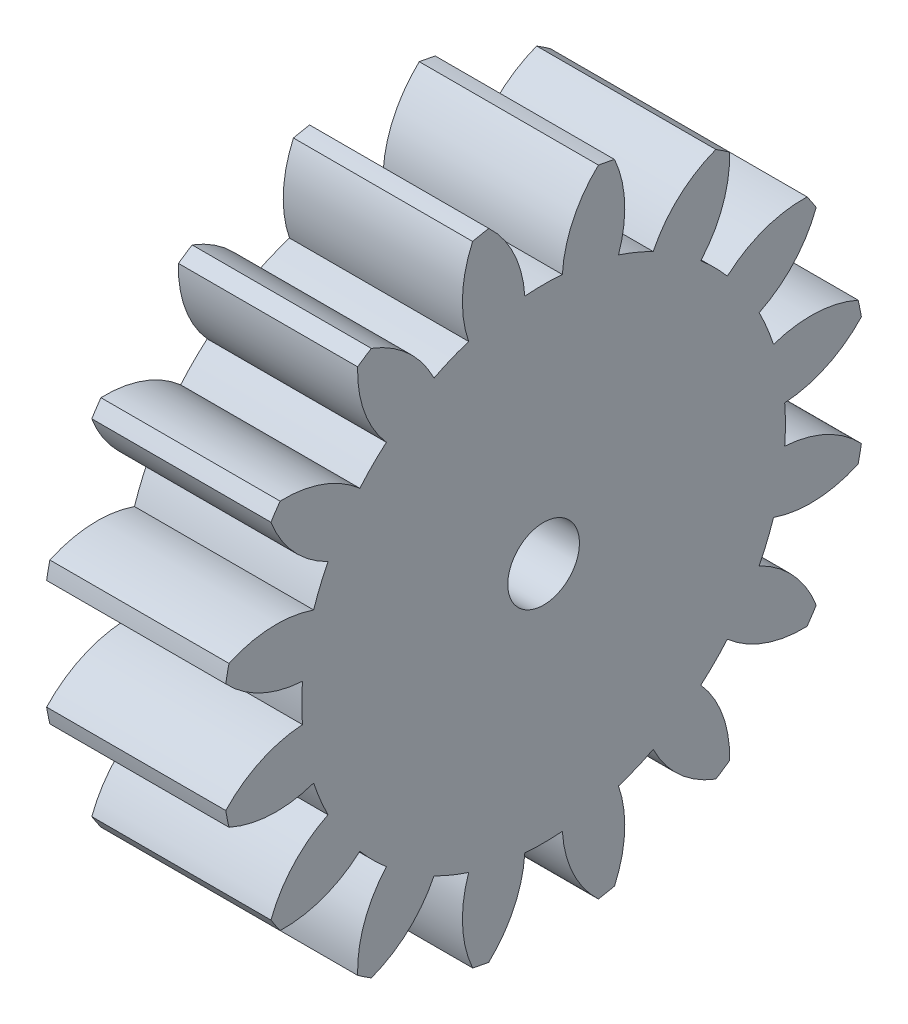
SolidWorks part; units mm, degrees
material "1.0035 (S185)"
ref_plane "Plane1" through (0, 0, 0) normal (0, 0, 1) x (1, 0, 0)
ref_plane "Plane2" through (0, 0, 0) normal (0, 1, 0) x (1, 0, 0)
ref_plane "Plane3" through (0, 0, 0) normal (1, 0, 0) x (0, 0, -1)
sketch "HoldingSke" plane through (0, 0, 0) normal (0, 1, 0) x (1, 0, 0)
  line L0 (0, 0) -> (0.9613, -0.2756)
  line L1 (-15, 0) -> (100, 0) construction
  line L2 (0, 0) -> (-2.1039, 2.3779)
  line L3 (0, 0) -> (-11.863, 4.5341)
  line L4 (0, 0) -> (8.3015, 2.3804)
  line L5 (0, 0) -> (-46.8476, -17.4728)
  line L6 (0, 0) -> (-4.1448, -2.7965)
  line L7 (-2.1039, 2.3779) -> (8.6586, 51.2059)
  line L8 (-76.2, 54.61) -> (-75.9, 54.61)
  line L9 (-71.009, 38.7566) -> (-53.1078, 45.2721)
  line L10 (-76.2, 71.12) -> (104.1128, 71.12)
  line L11 (0, 0) -> (-5, 0)
  line L12 (-76.2, 101.6) -> (-76.162, 101.6)
  line L13 (24.9733, 27.94) -> (52.9518, 28.4284)
  line L14 (24.9733, 27.94) -> (24.9743, 27.94)
  line L15 (24.9733, 27.94) -> (100.4006, 29.5858)
  line L16 (-63.627, -1) -> (-12.827, -1)
  circle A0 centre (0, 0) radius 1
  circle A1 centre (0, 0) radius 6.749
  circle A2 centre (0, 0) radius 37.5
  circle A3 centre (0, 0) radius 1
  dimension "MHD" = 13.498
  dimension "Hub_dia" = 75
  dimension "Bore" = 2
  dimension "MBD" = 2
  dimension "Num_teeth" = 16
  dimension "Pitch_radius" = 180.3128
  dimension "Pitch" = 1
  dimension "Width" = 5
  dimension "Overall_len" = 50
  dimension "Show_teeth" = 16
  dimension "Thickness" = 5
  dimension "OAL" = 50.0001
  dimension "T_dim" = 0.3
  dimension "Ap" = 20
  dimension "H" = 19.05
  dimension "Backlash" = 0.038
  dimension "Addendum_fac" = 1
  dimension "Dedendum_fac" = 1.25
  dimension "Clearance_fac" = 0.25
  dimension "Dedendum_add" = 0.001
  dimension "Module" = 1
sketch "BasProSke" plane through (0, 0, 0) normal (0, 1, 0) x (1, 0, 0)
  line L0 (-10, 0) -> (60, 0) construction
  line L1 (0, 0) -> (0, 9)
  line L2 (0, 0) -> (5, 0)
  line L3 (5, 0) -> (5, 9)
  line L4 (5, 9) -> (0, 9)
  dimension "Diameter" = 18
  dimension "Thickness" = 5
revolve "Base-Revolve" add sketch "BasProSke" angle 360 about L0
sketch "TooCutSke" plane through (0, 0, 0) normal (1, 0, 0) x (0, 0, -1)
  line L1 (0, 0) -> (0, 107) construction
  line L2 (0, 0) -> (-0.8506, 7.9547) construction
  line L3 (0, 0) -> (-3.1089, 15.6293) construction
  line L4 (-0.8506, 7.9547) -> (-1.5544, 7.8146) construction
  arc A0 (0.5238, 6.7286) -> (-0.5238, 6.7286) centre (0, 0) ccw
  arc A1 (1.5534, 8.8907) -> (-1.5534, 8.8907) centre (0, 0) ccw
  circle A2 centre (0, 0) radius 8 construction
  circle A3 centre (0, 0) radius 7.5175 construction
  arc A4 (-0.5238, 6.7286) -> (-1.5534, 8.8907) centre (-3.7179, 6.5338) ccw
  arc A5 (1.5534, 8.8907) -> (0.5238, 6.7286) centre (3.7179, 6.5338) ccw
  dimension "Root_dia" = 13.498
  dimension "Overcut_dia" = 18.0508
  dimension "Pitch_dia" = 16
  dimension "Base_dia" = 15.0351
  dimension "Flank_rad" = 3.2
  dimension "Half_ang" = 11.25
  dimension "Half_CT" = 0.7176
extrude "ToothCut" cut sketch "TooCutSke" along normal through all
fillet "Breaks" [suppressed] radius 0.02 tangent propagation no
fillet "RootFillets" [suppressed] radius 0.251
pattern_circular "TeethCuts" count 16 every 22.5 about axis through (-10, 0, 0) along (1, 0, 0) of "ToothCut", "RootFillets", "Breaks"
sketch "HubNeaOneSke" plane through (0, 0, 0) normal (-1, 0, 0) x (0, 0, 1)
  circle A0 centre (0, 0) radius 6.749
  dimension "Diameter" = 13.498
extrude "HubNearOne" [suppressed] add sketch "HubNeaOneSke" along normal blind 45.0001
sketch "HubNeaBotSke" plane through (0, 0, 0) normal (-1, 0, 0) x (0, 0, 1)
  circle A0 centre (0, 0) radius 6.749
  dimension "Diameter" = 13.498
extrude "HubNearBoth" [suppressed] add sketch "HubNeaBotSke" along normal blind 22.5
ref_plane "FarPln" through (5, 0, 0) normal (1, 0, 0) x (0, 0, -1)
sketch "HubFarSke" plane through (5, 0, 0) normal (1, 0, 0) x (0, 0, -1)
  circle A0 centre (0, 0) radius 6.749
  dimension "Diameter" = 13.498
extrude "HubFar" [suppressed] add sketch "HubFarSke" along normal blind 22.5
sketch "BorSke" plane through (0, 0, 0) normal (1, 0, 0) x (0, 0, -1)
  circle A0 centre (0, 0) radius 1
  dimension "Diameter" = 2
extrude "Bore" cut sketch "BorSke" along normal mid plane 100.0001
sketch "KeySke" plane through (0, 0, 0) normal (1, 0, 0) x (0, 0, -1)
  line L0 (-0.4, 0) -> (-0.4, 1.3)
  line L1 (-0.4, 1.3) -> (0.4, 1.3)
  line L2 (0.4, 1.3) -> (0.4, 0)
  line L3 (0, 0) -> (0, 34) construction
  line L4 (-0.4, 0) -> (0.4, 0)
  dimension "Offset" = 1.3
  dimension "Width" = 0.8
extrude "Keyway" [suppressed] cut sketch "KeySke" along normal mid plane 100.0001
pattern_circular "Keyway2" [suppressed] count 2 every 90 about axis through (-10, 0, 0) along (1, 0, 0)
ref_axis "Achse1" through (5, 0, 0) along (-1, 0, 0)
equation "' \"Module@HoldingSke\" = 6.35"
equation "' \"Num_teeth@HoldingSke\" = 12"
equation "' \"Ap@HoldingSke\" =  20"
equation "' \"Width@HoldingSke\" = 0.5 * 25.4"
equation "' \"Hub_dia@HoldingSke\"= 1 * 25.4"
equation "' \"Overall_len@HoldingSke\" = 1.0 * 25.4"
equation "' \"Bore@HoldingSke\" = 0.75 * 25.4"
equation "' \"T_dim@HoldingSke\" = 0.1 * 25.4"
equation "' \"Width@KeySke\" = 0.25 * 25.4"
equation "' \"Show_teeth@HoldingSke\" = 13"
equation "' \"Backlash@HoldingSke\" = 0.009 * 25.4"
equation "' \"Addendum_fac@HoldingSke\" = 1.0"
equation "' \"Dedendum_fac@HoldingSke\" = 1.25"
equation "' \"Dedendum_add@HoldingSke\" = 0.00005 * 25.4"
equation "' \"Clearance_fac@HoldingSke\" = 0.25"
equation "\"Pitch@HoldingSke\" = 1 / \"Module@HoldingSke\""
equation "\"Overcut_dia@TooCutSke\" = (\"Num_teeth@HoldingSke\" + 2 * \"Addendum_fac@HoldingSke\") / \"Pitch@HoldingSke\" + 0.002 * 25.4"
equation "\"Pitch_dia@TooCutSke\" = \"Num_teeth@HoldingSke\" / \"Pitch@HoldingSke\""
equation "\"Base_dia@TooCutSke\" = \"Num_teeth@HoldingSke\" / \"Pitch@HoldingSke\" * cos((\"Ap@HoldingSke\"  * 3.14159265 / 180))"
equation "\"Root_dia@TooCutSke\" = (\"Num_teeth@HoldingSke\" + 2) / \"Pitch@HoldingSke\" - 2 * (\"Addendum_fac@HoldingSke\" + \"Dedendum_fac@HoldingSke\") / \"Pitch@HoldingSke\" - \"Dedendum_add@HoldingSke\" * 2"
equation "\"Half_ang@TooCutSke\" = 180 / \"Num_teeth@HoldingSke\""
equation "\"Half_CT@TooCutSke\" = \"Num_teeth@HoldingSke\" / \"Pitch@HoldingSke\" * sin((3.14159265 / 2 / \"Num_teeth@HoldingSke\")) / 2 - 7 * \"Backlash@HoldingSke\" / 4"
equation "\"Flank_rad@TooCutSke\" = \"Num_teeth@HoldingSke\" / \"Pitch@HoldingSke\" / 5"
equation "\"Radius@RootFillets\" = \"Clearance_fac@HoldingSke\" / \"Pitch@HoldingSke\" + \"Dedendum_add@HoldingSke\""
equation "\"Break_rad@Breaks\" = 0.02 / \"Pitch@HoldingSke\""
equation "\"Thickness@HoldingSke\" = \"Width@HoldingSke\""
equation "\"OAL@HoldingSke\" = \"Thickness@HoldingSke\""
equation "\"MHD@HoldingSke\" = (\"Num_teeth@HoldingSke\" + 2) / \"Pitch@HoldingSke\" - 2 * (\"Addendum_fac@HoldingSke\" + \"Dedendum_fac@HoldingSke\")  / \"Pitch@HoldingSke\" - \"Dedendum_add@HoldingSke\" * 2"
equation "\"MBD@HoldingSke\" = (\"Num_teeth@HoldingSke\" + 2) / \"Pitch@HoldingSke\" - 2 * (\"Addendum_fac@HoldingSke\" + \"Dedendum_fac@HoldingSke\")  / \"Pitch@HoldingSke\" - \"Dedendum_add@HoldingSke\" * 2 - 0.002 * 25.4"
equation "\"MHD@HoldingSke\" = ((sgn( \"MHD@HoldingSke\" - \"Hub_dia@HoldingSke\" )-1)*( \"MHD@HoldingSke\" - \"Hub_dia@HoldingSke\" ))/-2+ \"Hub_dia@HoldingSke\""
equation "\"MBD@HoldingSke\" = ((sgn( \"MBD@HoldingSke\" - \"Bore@HoldingSke\" )-1)*( \"MBD@HoldingSke\" - \"Bore@HoldingSke\" ))/-2+ \"Bore@HoldingSke\""
equation "\"OAL@HoldingSke\" = ((sgn( \"OAL@HoldingSke\" - \"Overall_len@HoldingSke\" )+1)*( \"OAL@HoldingSke\" - \"Overall_len@HoldingSke\" ))/2 + \"Overall_len@HoldingSke\" + 0.000002 * 25.4"
equation "\"Num_teeth@TeethCuts\" = int( \"Show_teeth@HoldingSke\" ) + 1"
equation "\"Num_teeth@TeethCuts\" = ((sgn( \"Num_teeth@TeethCuts\" - \"Num_teeth@HoldingSke\" )-1)*( \"Num_teeth@TeethCuts\" - \"Num_teeth@HoldingSke\" ))/-2+ \"Num_teeth@HoldingSke\""
equation "\"Num_teeth@TeethCuts\" = ((sgn( \"Num_teeth@TeethCuts\" - 2.0)+1)*( \"Num_teeth@TeethCuts\" - 2.0))/2 +2.0"
equation "\"Angle@TeethCuts\" = 360.0 / \"Num_teeth@HoldingSke\""
equation "\"Diameter@BasProSke\" = (\"Num_teeth@HoldingSke\" + 2 * \"Addendum_fac@HoldingSke\") / \"Pitch@HoldingSke\""
equation "\"Thickness@BasProSke\"  = \"Thickness@HoldingSke\""
equation "' \"Fillet_rad@BasProSke\" =  \"Thickness@HoldingSke\" * 0.05"
equation "\"MHD@HoldingSke\" = ((sgn( \"MHD@HoldingSke\" - \"Root_dia@TooCutSke\" )-1)*( \"MHD@HoldingSke\" - \"Root_dia@TooCutSke\" ))/-2+ \"Root_dia@TooCutSke\""
equation "\"Diameter@HubNeaOneSke\" = \"MHD@HoldingSke\""
equation "\"Length@HubNearOne\" = \"OAL@HoldingSke\" - \"Thickness@BasProSke\""
equation "\"Diameter@HubNeaBotSke\" = \"MHD@HoldingSke\""
equation "\"Length@HubNearBoth\" = ( \"OAL@HoldingSke\" - \"Thickness@BasProSke\" ) / 2.0"
equation "\"Thickness@FarPln\" = \"Thickness@BasProSke\""
equation "\"Diameter@HubFarSke\" = \"MHD@HoldingSke\""
equation "\"Length@HubFar\" = ( \"OAL@HoldingSke\" - \"Thickness@BasProSke\" ) / 2.0"
equation "\"Diameter@BorSke\" = \"MBD@HoldingSke\""
equation "\"D1@Bore\" = \"OAL@HoldingSke\" * 2.0"
equation "\"D1@Keyway\" = \"OAL@HoldingSke\" * 2.0"
equation "\"Offset@KeySke\" = \"T_dim@HoldingSke\" + \"MBD@HoldingSke\" / 2.0"
